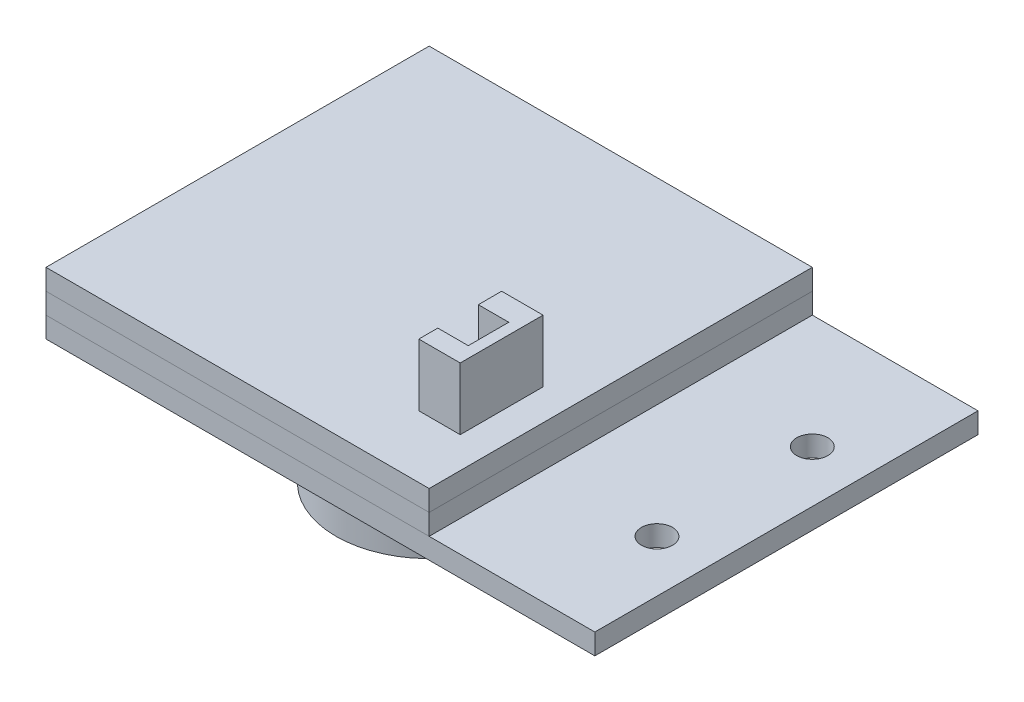
SolidWorks part; units mm, degrees
ref_plane "前视基准面" through (0, 0, 0) normal (0, 0, 1) x (1, 0, 0)
ref_plane "上视基准面" through (0, 0, 0) normal (0, 1, 0) x (1, 0, 0)
ref_plane "右视基准面" through (0, 0, 0) normal (1, 0, 0) x (0, 0, -1)
sketch "草图1" plane through (0, 0, 0) normal (0, 1, 0) x (1, 0, 0)
  line L0 (26.5, 0) -> (-26.5, 0) construction
  line L1 (-26.5, 18.5) -> (26.5, 18.5)
  line L2 (-26.5, 18.5) -> (-26.5, -18.5)
  line L3 (-26.5, -18.5) -> (26.5, -18.5)
  line L4 (26.5, 18.5) -> (26.5, -18.5)
  line L5 (-26.5, 18.5) -> (26.5, -18.5) construction
  line L6 (-26.5, -18.5) -> (26.5, 18.5) construction
  circle A0 centre (21.5, 7.5) radius 1.5
  circle A1 centre (21.5, -7.5) radius 1.5
  point P0 (0, 0)
  dimension "D3" = 3
  dimension "D4" = 5
  dimension "D5" = 15
  dimension "D1" = 37
  dimension "D2" = 53
extrude "凸台-拉伸1" add sketch "草图1" along normal blind 2
sketch "草图2" plane through (0, 2, 0) normal (0, 1, 0) x (1, 0, 0)
  line L0 (-26.5, -18.5) -> (26.5, -18.5) construction
  line L1 (-26.5, 18.5) -> (10.5, 18.5)
  line L2 (-26.5, 18.5) -> (-26.5, -18.5)
  line L3 (-26.5, -18.5) -> (10.5, -18.5)
  line L4 (10.5, 18.5) -> (10.5, -18.5)
  dimension "D1" = 37
extrude "凸台-拉伸2" add sketch "草图2" along normal blind 2 separate body
sketch "草图3" plane through (0, 4, 0) normal (0, 1, 0) x (1, 0, 0)
  line L4 (-26.5, 18.5) -> (-26.5, -18.5)
  line L5 (-26.5, -18.5) -> (10.5, -18.5)
  line L6 (10.5, -18.5) -> (10.5, 18.5)
  line L7 (10.5, 18.5) -> (-26.5, 18.5)
  line L8 (-26.5, 18.5) -> (-26.5, -18.5)
  line L9 (-26.5, -18.5) -> (10.5, -18.5)
  line L10 (10.5, -18.5) -> (10.5, 18.5)
  line L11 (10.5, 18.5) -> (-26.5, 18.5)
  dimension "D1" = 0
extrude "凸台-拉伸3" add sketch "草图3" along normal blind 2 separate body
sketch "草图4" plane through (0, 6, 0) normal (0, 1, 0) x (1, 0, 0)
  line L0 (-26.5, -18.5) -> (10.5, -18.5) construction
  line L1 (3.5, -12.5) -> (7.5, -12.5)
  line L2 (3.5, -12.5) -> (3.5, -4.5)
  line L3 (3.5, -4.5) -> (7.5, -4.5)
  line L4 (7.5, -12.5) -> (7.5, -4.5)
  line L5 (10.5, -18.5) -> (10.5, 18.5) construction
  line L7 (6.4412, -10.6649) -> (3.5, -10.6649)
  line L8 (6.4412, -10.6649) -> (6.4412, -6.7518)
  line L9 (6.4412, -6.7518) -> (3.5, -6.7518)
  line L10 (3.5, -10.6649) -> (3.5, -6.7518)
  line L11 (6.4412, -10.6649) -> (3.5, -6.7518) construction
  line L12 (6.4412, -6.7518) -> (3.5, -10.6649) construction
  point P8 (4.9706, -8.7084)
  dimension "D1" = 4
  dimension "D2" = 8
  dimension "D3" = 6
  dimension "D4" = 3
extrude "凸台-拉伸4" add sketch "草图4" along normal blind 6 contours L9 L8 L7 L2 L1 L4 L3 region at (3.5894, 6, 11.5825)
sketch "草图5" plane through (0, 0, 0) normal (0, -1, 0) x (1, 0, 0)
  line L0 (-8, -18.5) -> (-8, 18.5) construction
  line L1 (10.5, 0) -> (-26.5, 0) construction
  line L2 (-6, 11.5) -> (-6, 9.5)
  line L3 (-17.5, -9.5) -> (-10, -9.5)
  line L4 (-26.5, -18.5) -> (10.5, -18.5)
  line L5 (-26.5, 18.5) -> (-26.5, -18.5)
  line L6 (10.5, 18.5) -> (-26.5, 18.5)
  line L7 (10.5, -18.5) -> (10.5, 18.5)
  line L8 (-26.5, -18.5) -> (10.5, -18.5) construction
  line L9 (-26.5, 18.5) -> (-26.5, -18.5) construction
  line L10 (10.5, 18.5) -> (-26.5, 18.5) construction
  line L11 (10.5, -18.5) -> (10.5, 18.5) construction
  line L12 (-17.5, -9.5) -> (-17.5, 9.5)
  line L13 (-17.5, 9.5) -> (-10, 9.5)
  line L14 (1.5, -9.5) -> (1.5, 9.5)
  line L15 (-17.5, -9.5) -> (1.5, 9.5) construction
  line L16 (-17.5, 9.5) -> (1.5, -9.5) construction
  line L17 (-10, 11.5) -> (-10, 9.5)
  line L18 (-10, -11.5) -> (-10, -9.5)
  line L19 (-6, -11.5) -> (-6, -9.5)
  line L20 (-8, -9.5) -> (-6, -9.5) construction
  line L21 (-6, -9.5) -> (1.5, -9.5)
  line L22 (-10, -9.5) -> (-8, -9.5) construction
  line L23 (-8, 9.5) -> (-6, 9.5) construction
  line L24 (-6, 9.5) -> (1.5, 9.5)
  line L25 (-10, 9.5) -> (-8, 9.5) construction
  arc A0 (-6, 11.5) -> (-10, 11.5) centre (-8, 11.5) ccw
  circle A1 centre (-8, 11.5) radius 1
  circle A2 centre (-8, -11.5) radius 1
  arc A3 (-6, -11.5) -> (-10, -11.5) centre (-8, -11.5) cw
  arc A4 (-8, -9.5) -> (-6, -11.5) centre (-8, -11.5) cw construction
  arc A5 (-10, -11.5) -> (-8, -9.5) centre (-8, -11.5) cw construction
  arc A6 (-8, 9.5) -> (-6, 11.5) centre (-8, 11.5) ccw construction
  arc A7 (-10, 11.5) -> (-8, 9.5) centre (-8, 11.5) ccw construction
  point P8 (-8, 0)
  point P9 (-8, 0)
  dimension "D3" = 4
  dimension "D4" = 2
  dimension "D2" = 19
  dimension "D1" = 0
extrude "凸台-拉伸5" add sketch "草图5" along normal blind 4
sketch "草图6" plane through (0, -4, 0) normal (0, -1, 0) x (1, 0, 0)
  line L0 (-17.5, 9.5) -> (1.5, -9.5) construction
  line L1 (-17.5, -9.5) -> (-8, 0) construction
  circle A0 centre (-8, 0) radius 9
  dimension "D1" = 18
extrude "凸台-拉伸6" add sketch "草图6" along normal blind 8
sketch "草图7" plane through (0, -12, 0) normal (0, -1, 0) x (1, 0, 0)
  circle A0 centre (-8, 0) radius 6.6245
extrude "切除-拉伸1" cut sketch "草图7" against normal blind 2
ref_axis "基准轴1" through (-8, 8.2819, 0) along (0, -1, 0)
ref_plane "基准面1" through (-8, 0, 0) normal (1, 0, 0) x (0, -1, 0)
sketch "草图8" plane through (-8, 0, 0) normal (1, 0, 0) x (0, -1, 0)
  line L0 (10, 0) -> (11.7201, 0)
  line L1 (10, 0) -> (12, 0) construction
  line L2 (10, -6.6245) -> (10, 6.6245) construction
  line L3 (10, -6.6245) -> (10, 6.6245) construction
  line L4 (10, 0) -> (10, -6.6245)
  spline S0 degree 2 poles (10, -6.6245) (11.8598, -3.5864) (11.7201, 0) knots 0 0 0 1 1 1
revolve "旋转1" add sketch "草图8" angle 360 about L0
sketch "草图9" plane through (-8, 0, 0) normal (1, 0, 0) x (0, -1, 0)
  line L0 (6.2873, 0) -> (15.3777, 0) construction
  line L1 (10, 0) -> (12, 0) construction
  line L2 (4, -9) -> (12, -9) construction
  line L3 (6, -9) -> (7.5, -9)
  line L4 (6, -9) -> (6, -8.4234)
  line L5 (6.5, -7.9234) -> (7, -7.9234)
  line L6 (7.5, -9) -> (7.5, -8.4234)
  line L7 (4, -9) -> (4, 9) construction
  arc A0 (7, -7.9234) -> (7.5, -8.4234) centre (7, -8.4234) cw
  arc A1 (6, -8.4234) -> (6.5, -7.9234) centre (6.5, -8.4234) cw
  point P15 (7.5, -7.9234)
  point P18 (6, -7.9234)
  dimension "D3" = 0.5
  dimension "D1" = 1.5
  dimension "D2" = 2
revolve "切除-旋转1" cut sketch "草图9" angle 360 about L0
